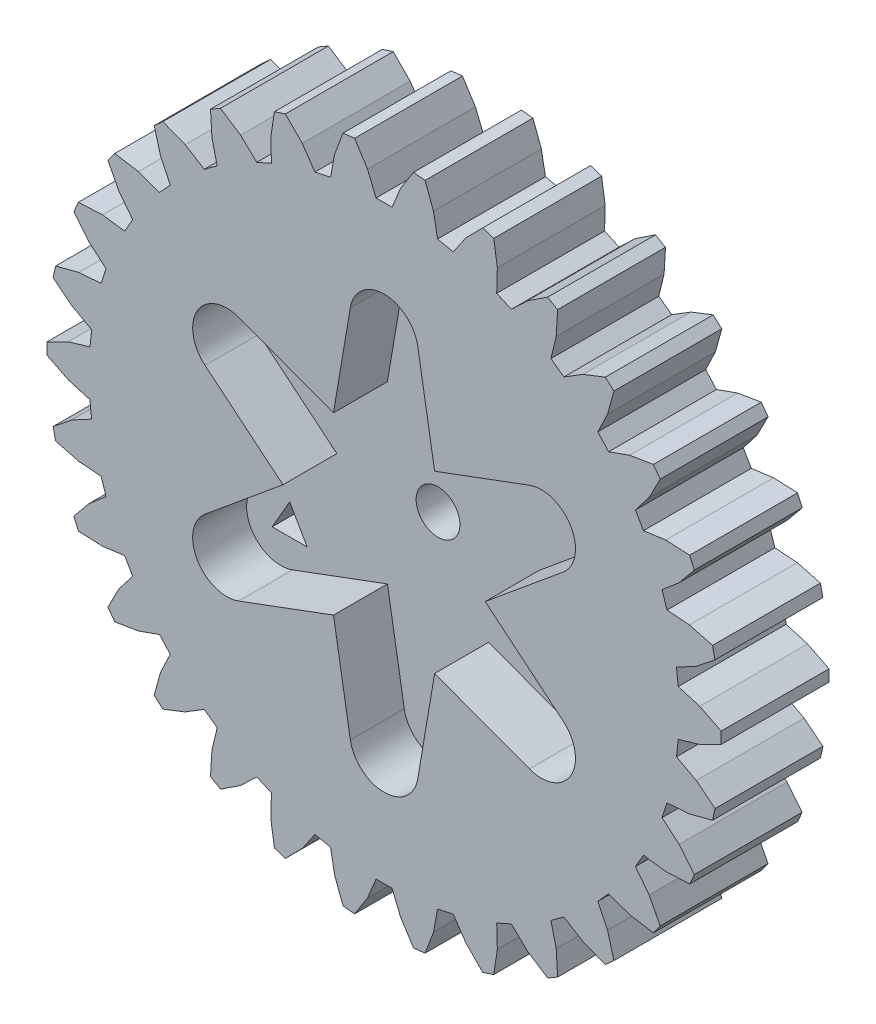
SolidWorks part; units mm, degrees
material "ABS"
ref_plane "Front Plane" through (0, 0, 0) normal (0, 0, 1) x (1, 0, 0)
ref_plane "Top Plane" through (0, 0, 0) normal (0, 1, 0) x (1, 0, 0)
ref_plane "Right Plane" through (0, 0, 0) normal (1, 0, 0) x (0, 0, -1)
sketch "Sketch1" plane through (0, 0, 0) normal (0, 0, 1) x (1, 0, 0)
  line L0 (67.8387, 65.5179) -> (69.435, 65.0497)
  line L1 (69.435, 65.0497) -> (71.0262, 64.252)
  line L2 (71.0262, 64.252) -> (71.0262, 63.394)
  line L3 (71.0262, 63.394) -> (69.435, 62.5962)
  line L4 (69.435, 62.5962) -> (67.8387, 62.1281)
  line L5 (67.8387, 62.1281) -> (67.7144, 60.9457)
  line L6 (67.7144, 60.9457) -> (69.1786, 60.156)
  line L7 (69.1786, 60.156) -> (70.5691, 59.0447)
  line L8 (70.5691, 59.0447) -> (70.3908, 58.2056)
  line L9 (70.3908, 58.2056) -> (68.6684, 57.756)
  line L10 (68.6684, 57.756) -> (67.0096, 57.6301)
  line L11 (67.0096, 57.6301) -> (66.6423, 56.4993)
  line L12 (66.6423, 56.4993) -> (67.9102, 55.4225)
  line L13 (67.9102, 55.4225) -> (69.0393, 54.0464)
  line L14 (69.0393, 54.0464) -> (68.6904, 53.2627)
  line L15 (68.6904, 53.2627) -> (66.9123, 53.181)
  line L16 (66.9123, 53.181) -> (65.2636, 53.4028)
  line L17 (65.2636, 53.4028) -> (64.669, 52.3732)
  line L18 (64.669, 52.3732) -> (65.6854, 51.0562)
  line L19 (65.6854, 51.0562) -> (66.5038, 49.4753)
  line L20 (66.5038, 49.4753) -> (65.9995, 48.7814)
  line L21 (65.9995, 48.7814) -> (64.2432, 49.0712)
  line L22 (64.2432, 49.0712) -> (62.6766, 49.6308)
  line L23 (62.6766, 49.6308) -> (61.8811, 48.7473)
  line L24 (61.8811, 48.7473) -> (62.6014, 47.2478)
  line L25 (62.6014, 47.2478) -> (63.0732, 45.5314)
  line L26 (63.0732, 45.5314) -> (62.4357, 44.9574)
  line L27 (62.4357, 44.9574) -> (60.778, 45.606)
  line L28 (60.778, 45.606) -> (59.3621, 46.4791)
  line L29 (59.3621, 46.4791) -> (58.4003, 45.7802)
  line L30 (58.4003, 45.7802) -> (58.793, 44.1638)
  line L31 (58.793, 44.1638) -> (58.8977, 42.3868)
  line L32 (58.8977, 42.3868) -> (58.1548, 41.9579)
  line L33 (58.1548, 41.9579) -> (56.6682, 42.9369)
  line L34 (56.6682, 42.9369) -> (55.4646, 44.0854)
  line L35 (55.4646, 44.0854) -> (54.3785, 43.6018)
  line L36 (54.3785, 43.6018) -> (54.4267, 41.939)
  line L37 (54.4267, 41.939) -> (54.1596, 40.1792)
  line L38 (54.1596, 40.1792) -> (53.3436, 39.914)
  line L39 (53.3436, 39.914) -> (52.0932, 41.1808)
  line L40 (52.0932, 41.1808) -> (51.1547, 42.5544)
  line L41 (51.1547, 42.5544) -> (49.9918, 42.3072)
  line L42 (49.9918, 42.3072) -> (49.6932, 40.6706)
  line L43 (49.6932, 40.6706) -> (49.066, 39.0048)
  line L44 (49.066, 39.0048) -> (48.2128, 38.9151)
  line L45 (48.2128, 38.9151) -> (47.253, 40.4142)
  line L46 (47.253, 40.4142) -> (46.6207, 41.9528)
  line L47 (46.6207, 41.9528) -> (45.4317, 41.9528)
  line L48 (45.4317, 41.9528) -> (44.7994, 40.4142)
  line L49 (44.7994, 40.4142) -> (43.8396, 38.9151)
  line L50 (43.8396, 38.9151) -> (42.9864, 39.0048)
  line L51 (42.9864, 39.0048) -> (42.3592, 40.6706)
  line L52 (42.3592, 40.6706) -> (42.0606, 42.3072)
  line L53 (42.0606, 42.3072) -> (40.8977, 42.5544)
  line L54 (40.8977, 42.5544) -> (39.9592, 41.1808)
  line L55 (39.9592, 41.1808) -> (38.7088, 39.914)
  line L56 (38.7088, 39.914) -> (37.8928, 40.1792)
  line L57 (37.8928, 40.1792) -> (37.6257, 41.939)
  line L58 (37.6257, 41.939) -> (37.6739, 43.6018)
  line L59 (37.6739, 43.6018) -> (36.5878, 44.0854)
  line L60 (36.5878, 44.0854) -> (35.3842, 42.9369)
  line L61 (35.3842, 42.9369) -> (33.8976, 41.9579)
  line L62 (33.8976, 41.9579) -> (33.1547, 42.3868)
  line L63 (33.1547, 42.3868) -> (33.2594, 44.1638)
  line L64 (33.2594, 44.1638) -> (33.6521, 45.7802)
  line L65 (33.6521, 45.7802) -> (32.6903, 46.4791)
  line L66 (32.6903, 46.4791) -> (31.2744, 45.606)
  line L67 (31.2744, 45.606) -> (29.6167, 44.9574)
  line L68 (29.6167, 44.9574) -> (28.9792, 45.5314)
  line L69 (28.9792, 45.5314) -> (29.451, 47.2478)
  line L70 (29.451, 47.2478) -> (30.1713, 48.7473)
  line L71 (30.1713, 48.7473) -> (29.3758, 49.6308)
  line L72 (29.3758, 49.6308) -> (27.8092, 49.0712)
  line L73 (27.8092, 49.0712) -> (26.0529, 48.7814)
  line L74 (26.0529, 48.7814) -> (25.5486, 49.4753)
  line L75 (25.5486, 49.4753) -> (26.367, 51.0562)
  line L76 (26.367, 51.0562) -> (27.3834, 52.3732)
  line L77 (27.3834, 52.3732) -> (26.7888, 53.4028)
  line L78 (26.7888, 53.4028) -> (25.1401, 53.181)
  line L79 (25.1401, 53.181) -> (23.362, 53.2627)
  line L80 (23.362, 53.2627) -> (23.0131, 54.0464)
  line L81 (23.0131, 54.0464) -> (24.1422, 55.4225)
  line L82 (24.1422, 55.4225) -> (25.4101, 56.4993)
  line L83 (25.4101, 56.4993) -> (25.0428, 57.6301)
  line L84 (25.0428, 57.6301) -> (23.384, 57.756)
  line L85 (23.384, 57.756) -> (21.6616, 58.2056)
  line L86 (21.6616, 58.2056) -> (21.4833, 59.0447)
  line L87 (21.4833, 59.0447) -> (22.8738, 60.156)
  line L88 (22.8738, 60.156) -> (24.338, 60.9457)
  line L89 (24.338, 60.9457) -> (24.2137, 62.1281)
  line L90 (24.2137, 62.1281) -> (22.6174, 62.5962)
  line L91 (22.6174, 62.5962) -> (21.0262, 63.394)
  line L92 (21.0262, 63.394) -> (21.0262, 64.252)
  line L93 (21.0262, 64.252) -> (22.6174, 65.0497)
  line L94 (22.6174, 65.0497) -> (24.2137, 65.5179)
  line L95 (24.2137, 65.5179) -> (24.338, 66.7003)
  line L96 (24.338, 66.7003) -> (22.8738, 67.49)
  line L97 (22.8738, 67.49) -> (21.4833, 68.6013)
  line L98 (21.4833, 68.6013) -> (21.6616, 69.4404)
  line L99 (21.6616, 69.4404) -> (23.384, 69.89)
  line L100 (23.384, 69.89) -> (25.0428, 70.0159)
  line L101 (25.0428, 70.0159) -> (25.4101, 71.1467)
  line L102 (25.4101, 71.1467) -> (24.1422, 72.2235)
  line L103 (24.1422, 72.2235) -> (23.0131, 73.5996)
  line L104 (23.0131, 73.5996) -> (23.362, 74.3832)
  line L105 (23.362, 74.3832) -> (25.1401, 74.465)
  line L106 (25.1401, 74.465) -> (26.7888, 74.2432)
  line L107 (26.7888, 74.2432) -> (27.3834, 75.2728)
  line L108 (27.3834, 75.2728) -> (26.367, 76.5898)
  line L109 (26.367, 76.5898) -> (25.5486, 78.1707)
  line L110 (25.5486, 78.1707) -> (26.0529, 78.8646)
  line L111 (26.0529, 78.8646) -> (27.8092, 78.5748)
  line L112 (27.8092, 78.5748) -> (29.3758, 78.0151)
  line L113 (29.3758, 78.0151) -> (30.1713, 78.8987)
  line L114 (30.1713, 78.8987) -> (29.451, 80.3982)
  line L115 (29.451, 80.3982) -> (28.9792, 82.1145)
  line L116 (28.9792, 82.1145) -> (29.6167, 82.6886)
  line L117 (29.6167, 82.6886) -> (31.2744, 82.04)
  line L118 (31.2744, 82.04) -> (32.6903, 81.1669)
  line L119 (32.6903, 81.1669) -> (33.6521, 81.8658)
  line L120 (33.6521, 81.8658) -> (33.2594, 83.4822)
  line L121 (33.2594, 83.4822) -> (33.1547, 85.2592)
  line L122 (33.1547, 85.2592) -> (33.8976, 85.6881)
  line L123 (33.8976, 85.6881) -> (35.3842, 84.7091)
  line L124 (35.3842, 84.7091) -> (36.5878, 83.5606)
  line L125 (36.5878, 83.5606) -> (37.6739, 84.0442)
  line L126 (37.6739, 84.0442) -> (37.6257, 85.707)
  line L127 (37.6257, 85.707) -> (37.8928, 87.4668)
  line L128 (37.8928, 87.4668) -> (38.7088, 87.732)
  line L129 (38.7088, 87.732) -> (39.9592, 86.4652)
  line L130 (39.9592, 86.4652) -> (40.8977, 85.0916)
  line L131 (40.8977, 85.0916) -> (42.0606, 85.3388)
  line L132 (42.0606, 85.3388) -> (42.3592, 86.9754)
  line L133 (42.3592, 86.9754) -> (42.9864, 88.6412)
  line L134 (42.9864, 88.6412) -> (43.8396, 88.7309)
  line L135 (43.8396, 88.7309) -> (44.7994, 87.2318)
  line L136 (44.7994, 87.2318) -> (45.4317, 85.6932)
  line L137 (45.4317, 85.6932) -> (46.6207, 85.6932)
  line L138 (46.6207, 85.6932) -> (47.253, 87.2318)
  line L139 (47.253, 87.2318) -> (48.2128, 88.7309)
  line L140 (48.2128, 88.7309) -> (49.066, 88.6412)
  line L141 (49.066, 88.6412) -> (49.6932, 86.9754)
  line L142 (49.6932, 86.9754) -> (49.9918, 85.3388)
  line L143 (49.9918, 85.3388) -> (51.1547, 85.0916)
  line L144 (51.1547, 85.0916) -> (52.0932, 86.4652)
  line L145 (52.0932, 86.4652) -> (53.3436, 87.732)
  line L146 (53.3436, 87.732) -> (54.1596, 87.4668)
  line L147 (54.1596, 87.4668) -> (54.4267, 85.707)
  line L148 (54.4267, 85.707) -> (54.3785, 84.0442)
  line L149 (54.3785, 84.0442) -> (55.4646, 83.5606)
  line L150 (55.4646, 83.5606) -> (56.6682, 84.7091)
  line L151 (56.6682, 84.7091) -> (58.1548, 85.6881)
  line L152 (58.1548, 85.6881) -> (58.8977, 85.2592)
  line L153 (58.8977, 85.2592) -> (58.793, 83.4822)
  line L154 (58.793, 83.4822) -> (58.4003, 81.8658)
  line L155 (58.4003, 81.8658) -> (59.3621, 81.1669)
  line L156 (59.3621, 81.1669) -> (60.778, 82.04)
  line L157 (60.778, 82.04) -> (62.4357, 82.6886)
  line L158 (62.4357, 82.6886) -> (63.0732, 82.1145)
  line L159 (63.0732, 82.1145) -> (62.6014, 80.3982)
  line L160 (62.6014, 80.3982) -> (61.8811, 78.8987)
  line L161 (61.8811, 78.8987) -> (62.6766, 78.0151)
  line L162 (62.6766, 78.0151) -> (64.2432, 78.5748)
  line L163 (64.2432, 78.5748) -> (65.9995, 78.8646)
  line L164 (65.9995, 78.8646) -> (66.5038, 78.1707)
  line L165 (66.5038, 78.1707) -> (65.6854, 76.5898)
  line L166 (65.6854, 76.5898) -> (64.669, 75.2728)
  line L167 (64.669, 75.2728) -> (65.2636, 74.2432)
  line L168 (65.2636, 74.2432) -> (66.9123, 74.465)
  line L169 (66.9123, 74.465) -> (68.6904, 74.3832)
  line L170 (68.6904, 74.3832) -> (69.0393, 73.5996)
  line L171 (69.0393, 73.5996) -> (67.9102, 72.2235)
  line L172 (67.9102, 72.2235) -> (66.6423, 71.1467)
  line L173 (66.6423, 71.1467) -> (67.0096, 70.0159)
  line L174 (67.0096, 70.0159) -> (68.6684, 69.89)
  line L175 (68.6684, 69.89) -> (70.3908, 69.4404)
  line L176 (70.3908, 69.4404) -> (70.5691, 68.6013)
  line L177 (70.5691, 68.6013) -> (69.1786, 67.49)
  line L178 (69.1786, 67.49) -> (67.7144, 66.7003)
  line L179 (67.7144, 66.7003) -> (67.8387, 65.5179)
  line L180 (48.6394, 38.96) -> (43.413, 88.686) construction
  line L181 (21.0262, 63.823) -> (71.0262, 63.823) construction
  point P184 (46.0262, 63.823)
sketch "Sketch3" plane through (0, 0, 0) normal (0, 0, 1) x (1, 0, 0)
  circle A0 centre (46.0262, 63.823) radius 18
  dimension "D1" = 36
sketch "Sketch4" plane through (0, 0, 0) normal (0, 0, 1) x (1, 0, 0)
  line L0 (42.2762, 70.3182) -> (46.0262, 63.823) construction
  line L1 (48.6394, 38.96) -> (43.413, 88.686) construction
  line L2 (46.0262, 63.823) -> (46.0262, 79.823) construction
  line L3 (42.2762, 70.3182) -> (43.5262, 77.7103)
  line L4 (49.7762, 70.3182) -> (48.5262, 77.7103)
  line L5 (46.0262, 63.823) -> (49.7762, 70.3182) construction
  line L6 (49.7762, 70.3182) -> (56.8029, 72.9317)
  line L7 (53.5262, 63.823) -> (59.3029, 68.6016)
  line L8 (53.5262, 63.823) -> (59.3029, 59.0444)
  line L9 (49.7762, 57.3278) -> (56.8029, 54.7143)
  line L10 (49.7762, 57.3278) -> (48.5262, 49.9357)
  line L11 (42.2762, 57.3278) -> (43.5262, 49.9357)
  line L12 (42.2762, 57.3278) -> (35.2495, 54.7143)
  line L13 (38.5262, 63.823) -> (32.7495, 59.0444)
  line L14 (38.5262, 63.823) -> (32.7495, 68.6016)
  line L15 (42.2762, 70.3182) -> (35.2495, 72.9317)
  arc A0 (48.5262, 77.7103) -> (43.5262, 77.7103) centre (46.0262, 77.2875) ccw
  circle A1 centre (46.0262, 63.823) radius 7.5 construction
  arc A2 (59.3029, 68.6016) -> (56.8029, 72.9317) centre (57.6868, 70.5553) ccw
  circle A3 centre (46.0262, 63.823) radius 7.5 construction
  arc A4 (56.8029, 54.7143) -> (59.3029, 59.0444) centre (57.6868, 57.0907) ccw
  circle A5 centre (46.0262, 63.823) radius 7.5 construction
  arc A6 (43.5262, 49.9357) -> (48.5262, 49.9357) centre (46.0262, 50.3585) ccw
  circle A7 centre (46.0262, 63.823) radius 7.5 construction
  arc A8 (32.7495, 59.0444) -> (35.2495, 54.7143) centre (34.3656, 57.0907) ccw
  circle A9 centre (46.0262, 63.823) radius 7.5 construction
  arc A10 (35.2495, 72.9317) -> (32.7495, 68.6016) centre (34.3656, 70.5553) ccw
  circle A11 centre (46.0262, 63.823) radius 7.5 construction
  point P0 (46.0262, 63.823)
  point P43 (46.0262, 63.823)
  dimension "D1" = 16
  dimension "D2" = 6
  dimension "D3" = 7.5
  dimension "D4" = 5
extrude "Boss-Extrude1" add sketch "Sketch1" against normal blind 8
sketch "Sketch5" plane through (0, 0, 0) normal (0, 0, 1) x (1, 0, 0)
  circle A0 centre (46.0262, 63.823) radius 1.625
  point P0 (46.0262, 63.823)
  dimension "D1" = 3.25
sketch "Sketch7" plane through (0, 0, -8) normal (0, 0, -1) x (-1, 0, 0)
  circle A0 centre (-46.0262, 63.823) radius 2.875
  point P0 (-46.0262, 63.823)
  dimension "D1" = 5.75
extrude "Cut-Extrude4" cut sketch "Sketch4" against normal blind 4
extrude "Cut-Extrude5" cut sketch "Sketch5" against normal through all
extrude "Cut-Extrude6" cut sketch "Sketch7" against normal blind 1.5
sketch "Sketch9" plane through (0, 0, 0) normal (0, 0, 1) x (1, 0, 0)
  line L0 (46.0262, 63.823) -> (46.0262, 81.823) construction
  line L1 (57.0247, 58.973) -> (55.7257, 56.723)
  line L2 (47.3252, 75.773) -> (46.0262, 78.023)
  line L3 (46.0262, 78.023) -> (44.7272, 75.773)
  line L4 (44.7272, 75.773) -> (47.3252, 75.773)
  line L5 (55.7257, 56.723) -> (58.3238, 56.723)
  line L6 (58.3238, 56.723) -> (57.0247, 58.973)
  line L7 (46.0262, 63.823) -> (61.6147, 54.823) construction
  line L8 (36.3267, 56.723) -> (35.0277, 58.973)
  line L9 (35.0277, 58.973) -> (33.7286, 56.723)
  line L10 (33.7286, 56.723) -> (36.3267, 56.723)
  line L11 (46.0262, 63.823) -> (30.4377, 54.823) construction
  circle A0 centre (46.0262, 63.823) radius 18 construction
  circle A1 centre (46.0262, 76.523) radius 0.75 construction
  point P0 (46.0262, 63.823)
  point P22 (46.0262, 63.823)
  dimension "D1" = 1.5
  dimension "D2" = 12.7
  dimension "D3" = 3
extrude "Cut-Extrude7" cut sketch "Sketch9" against normal through all
